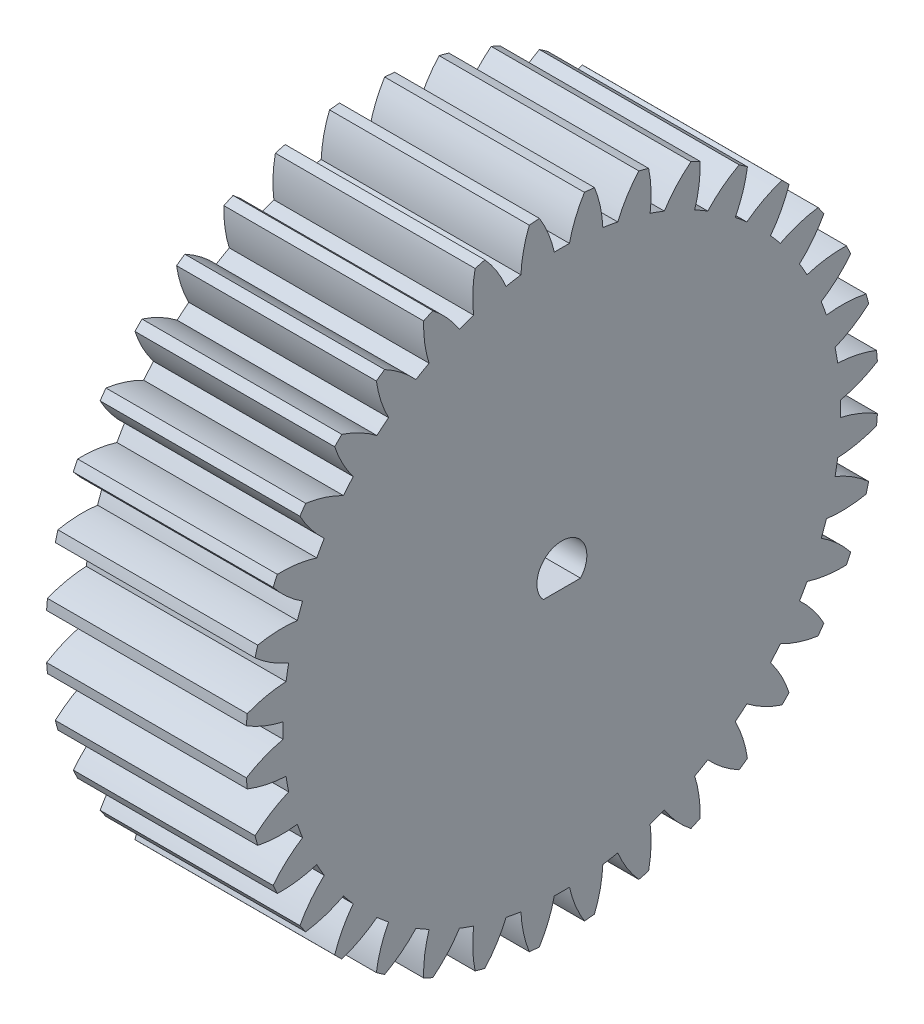
SolidWorks part; units mm, degrees
ref_plane "Plane1" through (0, 0, 0) normal (0, 0, 1) x (1, 0, 0)
ref_plane "Plane2" through (0, 0, 0) normal (0, 1, 0) x (1, 0, 0)
ref_plane "Plane3" through (0, 0, 0) normal (1, 0, 0) x (0, 0, -1)
sketch "HoldingSke" plane through (0, 0, 0) normal (0, 1, 0) x (1, 0, 0)
  line L0 (0, 0) -> (0.809, -0.5878)
  line L1 (-15, 0) -> (100, 0) construction
  line L2 (0, 0) -> (-2.1039, 2.3779)
  line L3 (0, 0) -> (-11.863, 4.5341)
  line L4 (0, 0) -> (6.9867, 5.0761)
  line L5 (0, 0) -> (-46.8476, -17.4728)
  line L6 (0, 0) -> (-9.9476, -6.7116)
  line L7 (-2.1039, 2.3779) -> (8.6586, 51.2059)
  line L8 (-76.2, 54.61) -> (-75.7, 54.61)
  line L9 (-71.009, 38.7566) -> (-53.1078, 45.2721)
  line L10 (-76.2, 71.12) -> (104.1128, 71.12)
  line L11 (0, 0) -> (-12, 0)
  line L12 (-76.2, 101.6) -> (-76.162, 101.6)
  line L13 (24.9733, 27.94) -> (52.9518, 28.4284)
  line L14 (24.9733, 27.94) -> (24.9743, 27.94)
  line L15 (24.9733, 27.94) -> (100.4006, 29.5858)
  line L16 (-63.627, -1) -> (-12.827, -1)
  circle A0 centre (0, 0) radius 1.5
  circle A1 centre (0, 0) radius 16.749
  circle A2 centre (0, 0) radius 37.5
  circle A3 centre (0, 0) radius 1.5
  dimension "MHD" = 33.498
  dimension "Hub_dia" = 75
  dimension "Bore" = 3
  dimension "MBD" = 3
  dimension "Num_teeth" = 36
  dimension "Pitch_radius" = 180.3128
  dimension "Pitch" = 1
  dimension "Width" = 12
  dimension "Overall_len" = 50
  dimension "Show_teeth" = 36
  dimension "Thickness" = 12
  dimension "OAL" = 50.0001
  dimension "T_dim" = 0.5
  dimension "Ap" = 20
  dimension "H" = 19.05
  dimension "Backlash" = 0.038
  dimension "Addendum_fac" = 1
  dimension "Dedendum_fac" = 1.25
  dimension "Clearance_fac" = 0.25
  dimension "Dedendum_add" = 0.001
  dimension "Module" = 1
sketch "BasProSke" plane through (0, 0, 0) normal (0, 1, 0) x (1, 0, 0)
  line L0 (-10, 0) -> (60, 0) construction
  line L1 (0, 0) -> (0, 19)
  line L2 (0, 0) -> (12, 0)
  line L3 (12, 0) -> (12, 19)
  line L4 (12, 19) -> (0, 19)
  dimension "Diameter" = 38
  dimension "Thickness" = 12
revolve "Base-Revolve" add sketch "BasProSke" angle 360 about L0
sketch "TooCutSke" plane through (0, 0, 0) normal (1, 0, 0) x (0, 0, -1)
  line L1 (0, 0) -> (0, 107) construction
  line L2 (0, 0) -> (-0.8516, 17.9798) construction
  line L3 (0, 0) -> (-3.1351, 35.8344) construction
  line L4 (-0.8516, 17.9798) -> (-1.5676, 17.9172) construction
  arc A0 (0.4547, 16.7428) -> (-0.4547, 16.7428) centre (0, 0) ccw
  arc A1 (1.3689, 18.9761) -> (-1.3689, 18.9761) centre (0, 0) ccw
  circle A2 centre (0, 0) radius 18 construction
  circle A3 centre (0, 0) radius 16.9145 construction
  arc A4 (-0.4547, 16.7428) -> (-1.3689, 18.9761) centre (-7.4808, 15.1702) ccw
  arc A5 (1.3689, 18.9761) -> (0.4547, 16.7428) centre (7.4808, 15.1702) ccw
  dimension "Root_dia" = 33.498
  dimension "Overcut_dia" = 38.0508
  dimension "Pitch_dia" = 36
  dimension "Base_dia" = 33.8289
  dimension "Flank_rad" = 7.2
  dimension "Half_ang" = 5
  dimension "Half_CT" = 0.7186
extrude "ToothCut" cut sketch "TooCutSke" along normal through all
fillet "Breaks" [suppressed] radius 0.02 tangent propagation no
fillet "RootFillets" [suppressed] radius 0.251
pattern_circular "TeethCuts" count 36 every 10 about axis through (-10, 0, 0) along (1, 0, 0) of "ToothCut", "RootFillets", "Breaks"
sketch "HubNeaOneSke" plane through (0, 0, 0) normal (-1, 0, 0) x (0, 0, 1)
  circle A0 centre (0, 0) radius 16.749
  dimension "Diameter" = 33.498
extrude "HubNearOne" [suppressed] add sketch "HubNeaOneSke" along normal blind 38.0001
sketch "HubNeaBotSke" plane through (0, 0, 0) normal (-1, 0, 0) x (0, 0, 1)
  circle A0 centre (0, 0) radius 16.749
  dimension "Diameter" = 33.498
extrude "HubNearBoth" [suppressed] add sketch "HubNeaBotSke" along normal blind 19
ref_plane "FarPln" through (12, 0, 0) normal (1, 0, 0) x (0, 0, -1)
sketch "HubFarSke" plane through (12, 0, 0) normal (1, 0, 0) x (0, 0, -1)
  circle A0 centre (0, 0) radius 16.749
  dimension "Diameter" = 33.498
extrude "HubFar" [suppressed] add sketch "HubFarSke" along normal blind 19
sketch "BorSke" plane through (0, 0, 0) normal (1, 0, 0) x (0, 0, -1)
  circle A0 centre (0, 0) radius 1.5
  dimension "Diameter" = 3
extrude "Bore" cut sketch "BorSke" along normal mid plane 100.0001
sketch "KeySke" plane through (0, 0, 0) normal (1, 0, 0) x (0, 0, -1)
  line L0 (-0.6, 0) -> (-0.6, 2)
  line L1 (-0.6, 2) -> (0.6, 2)
  line L2 (0.6, 2) -> (0.6, 0)
  line L3 (0, 0) -> (0, 34) construction
  line L4 (-0.6, 0) -> (0.6, 0)
  dimension "Offset" = 2
  dimension "Width" = 1.2
extrude "Keyway" [suppressed] cut sketch "KeySke" along normal mid plane 100.0001
pattern_circular "Keyway2" [suppressed] count 2 every 90 about axis through (-10, 0, 0) along (1, 0, 0)
sketch "Sketch1" plane through (12, 0, 0) normal (1, 0, 0) x (0, 0, -1)
  line L1 (-1.118, -1) -> (1.9519, -1)
  line L2 (-1.118, -1) -> (-1.118, -2.2207)
  line L3 (-1.118, -2.2207) -> (1.9519, -2.2207)
  line L4 (1.9519, -1) -> (1.9519, -2.2207)
  circle A0 centre (0, 0) radius 1.5 construction
  dimension "D1" = 1
extrude "Boss-Extrude1" add sketch "Sketch1" against normal through all
equation "' \"Module@HoldingSke\" = 6.35"
equation "' \"Num_teeth@HoldingSke\" = 12"
equation "' \"Ap@HoldingSke\" =  20"
equation "' \"Width@HoldingSke\" = 0.5 * 25.4"
equation "' \"Hub_dia@HoldingSke\"= 1 * 25.4"
equation "' \"Overall_len@HoldingSke\" = 1.0 * 25.4"
equation "' \"Bore@HoldingSke\" = 0.75 * 25.4"
equation "' \"T_dim@HoldingSke\" = 0.1 * 25.4"
equation "' \"Width@KeySke\" = 0.25 * 25.4"
equation "' \"Show_teeth@HoldingSke\" = 13"
equation "' \"Backlash@HoldingSke\" = 0.009 * 25.4"
equation "' \"Addendum_fac@HoldingSke\" = 1.0"
equation "' \"Dedendum_fac@HoldingSke\" = 1.25"
equation "' \"Dedendum_add@HoldingSke\" = 0.00005 * 25.4"
equation "' \"Clearance_fac@HoldingSke\" = 0.25"
equation "\"Pitch@HoldingSke\" = 1 / \"Module@HoldingSke\""
equation "\"Overcut_dia@TooCutSke\" = (\"Num_teeth@HoldingSke\" + 2 * \"Addendum_fac@HoldingSke\") / \"Pitch@HoldingSke\" + 0.002 * 25.4"
equation "\"Pitch_dia@TooCutSke\" = \"Num_teeth@HoldingSke\" / \"Pitch@HoldingSke\""
equation "\"Base_dia@TooCutSke\" = \"Num_teeth@HoldingSke\" / \"Pitch@HoldingSke\" * cos((\"Ap@HoldingSke\"  * 3.14159265 / 180))"
equation "\"Root_dia@TooCutSke\" = (\"Num_teeth@HoldingSke\" + 2) / \"Pitch@HoldingSke\" - 2 * (\"Addendum_fac@HoldingSke\" + \"Dedendum_fac@HoldingSke\") / \"Pitch@HoldingSke\" - \"Dedendum_add@HoldingSke\" * 2"
equation "\"Half_ang@TooCutSke\" = 180 / \"Num_teeth@HoldingSke\""
equation "\"Half_CT@TooCutSke\" = \"Num_teeth@HoldingSke\" / \"Pitch@HoldingSke\" * sin((3.14159265 / 2 / \"Num_teeth@HoldingSke\")) / 2 - 7 * \"Backlash@HoldingSke\" / 4"
equation "\"Flank_rad@TooCutSke\" = \"Num_teeth@HoldingSke\" / \"Pitch@HoldingSke\" / 5"
equation "\"Radius@RootFillets\" = \"Clearance_fac@HoldingSke\" / \"Pitch@HoldingSke\" + \"Dedendum_add@HoldingSke\""
equation "\"Break_rad@Breaks\" = 0.02 / \"Pitch@HoldingSke\""
equation "\"Thickness@HoldingSke\" = \"Width@HoldingSke\""
equation "\"OAL@HoldingSke\" = \"Thickness@HoldingSke\""
equation "\"MHD@HoldingSke\" = (\"Num_teeth@HoldingSke\" + 2) / \"Pitch@HoldingSke\" - 2 * (\"Addendum_fac@HoldingSke\" + \"Dedendum_fac@HoldingSke\")  / \"Pitch@HoldingSke\" - \"Dedendum_add@HoldingSke\" * 2"
equation "\"MBD@HoldingSke\" = (\"Num_teeth@HoldingSke\" + 2) / \"Pitch@HoldingSke\" - 2 * (\"Addendum_fac@HoldingSke\" + \"Dedendum_fac@HoldingSke\")  / \"Pitch@HoldingSke\" - \"Dedendum_add@HoldingSke\" * 2 - 0.002 * 25.4"
equation "\"MHD@HoldingSke\" = ((sgn( \"MHD@HoldingSke\" - \"Hub_dia@HoldingSke\" )-1)*( \"MHD@HoldingSke\" - \"Hub_dia@HoldingSke\" ))/-2+ \"Hub_dia@HoldingSke\""
equation "\"MBD@HoldingSke\" = ((sgn( \"MBD@HoldingSke\" - \"Bore@HoldingSke\" )-1)*( \"MBD@HoldingSke\" - \"Bore@HoldingSke\" ))/-2+ \"Bore@HoldingSke\""
equation "\"OAL@HoldingSke\" = ((sgn( \"OAL@HoldingSke\" - \"Overall_len@HoldingSke\" )+1)*( \"OAL@HoldingSke\" - \"Overall_len@HoldingSke\" ))/2 + \"Overall_len@HoldingSke\" + 0.000002 * 25.4"
equation "\"Num_teeth@TeethCuts\" = int( \"Show_teeth@HoldingSke\" ) + 1"
equation "\"Num_teeth@TeethCuts\" = ((sgn( \"Num_teeth@TeethCuts\" - \"Num_teeth@HoldingSke\" )-1)*( \"Num_teeth@TeethCuts\" - \"Num_teeth@HoldingSke\" ))/-2+ \"Num_teeth@HoldingSke\""
equation "\"Num_teeth@TeethCuts\" = ((sgn( \"Num_teeth@TeethCuts\" - 2.0)+1)*( \"Num_teeth@TeethCuts\" - 2.0))/2 +2.0"
equation "\"Angle@TeethCuts\" = 360.0 / \"Num_teeth@HoldingSke\""
equation "\"Diameter@BasProSke\" = (\"Num_teeth@HoldingSke\" + 2 * \"Addendum_fac@HoldingSke\") / \"Pitch@HoldingSke\""
equation "\"Thickness@BasProSke\"  = \"Thickness@HoldingSke\""
equation "' \"Fillet_rad@BasProSke\" =  \"Thickness@HoldingSke\" * 0.05"
equation "\"MHD@HoldingSke\" = ((sgn( \"MHD@HoldingSke\" - \"Root_dia@TooCutSke\" )-1)*( \"MHD@HoldingSke\" - \"Root_dia@TooCutSke\" ))/-2+ \"Root_dia@TooCutSke\""
equation "\"Diameter@HubNeaOneSke\" = \"MHD@HoldingSke\""
equation "\"Length@HubNearOne\" = \"OAL@HoldingSke\" - \"Thickness@BasProSke\""
equation "\"Diameter@HubNeaBotSke\" = \"MHD@HoldingSke\""
equation "\"Length@HubNearBoth\" = ( \"OAL@HoldingSke\" - \"Thickness@BasProSke\" ) / 2.0"
equation "\"Thickness@FarPln\" = \"Thickness@BasProSke\""
equation "\"Diameter@HubFarSke\" = \"MHD@HoldingSke\""
equation "\"Length@HubFar\" = ( \"OAL@HoldingSke\" - \"Thickness@BasProSke\" ) / 2.0"
equation "\"Diameter@BorSke\" = \"MBD@HoldingSke\""
equation "\"D1@Bore\" = \"OAL@HoldingSke\" * 2.0"
equation "\"D1@Keyway\" = \"OAL@HoldingSke\" * 2.0"
equation "\"Offset@KeySke\" = \"T_dim@HoldingSke\" + \"MBD@HoldingSke\" / 2.0"
